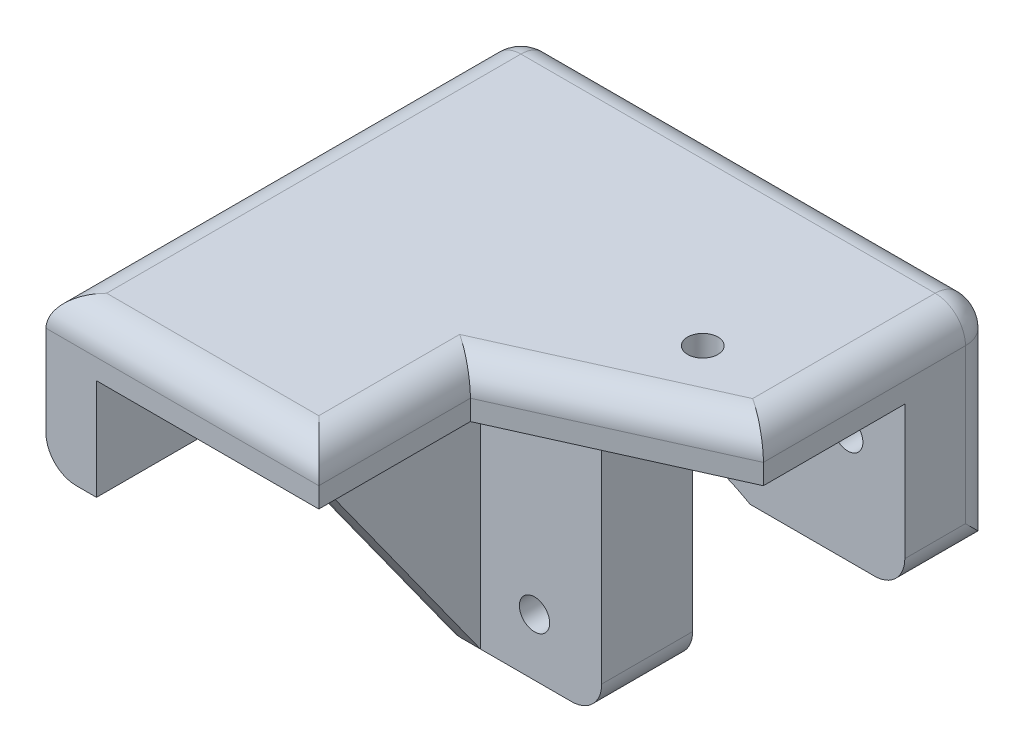
SolidWorks part; units mm, degrees
ref_plane "Front Plane" through (0, 0, 0) normal (0, 0, 1) x (1, 0, 0)
ref_plane "Top Plane" through (0, 0, 0) normal (0, 1, 0) x (1, 0, 0)
ref_plane "Right Plane" through (0, 0, 0) normal (1, 0, 0) x (0, 0, -1)
sketch "Sketch2" plane through (0, 0, 0) normal (0, 0, 1) x (1, 0, 0)
  line L0 (0, 0) -> (0, 47)
  line L1 (0, 47) -> (47, 47)
  line L2 (47, 47) -> (47, 25.75)
  line L3 (47, 25.75) -> (31.68, 25.75)
  line L4 (17, 0) -> (17, 27.58)
  line L5 (17, 0) -> (0, 0)
  arc A0 (17, 27.58) -> (31.68, 25.75) centre (22.2111, 9.5871) cw
  dimension "D1" = 47
  dimension "D2" = 47
  dimension "D3" = 21.25
  dimension "D4" = 17
  dimension "D5" = 27.58
  dimension "D6" = 15.32
extrude "Boss-Extrude1" add sketch "Sketch2" along normal blind 9
sketch "Sketch3" plane through (0, 0, 9) normal (0, 0, 1) x (1, 0, 0)
  line L0 (0, 0) -> (17, 0) construction
  line L1 (0, 47) -> (0, 0) construction
  line L3 (47, 47) -> (0, 47) construction
  circle A0 centre (10.35, 5.65) radius 1.5
  circle A1 centre (10.35, 36.65) radius 1.5
  circle A2 centre (41.35, 36.65) radius 1.5
  dimension "D1" = 3
  dimension "D5" = 3
  dimension "D6" = 3
  dimension "D2" = 5.65
  dimension "D3" = 10.35
  dimension "D4" = 31
  dimension "D7" = 10.35
  dimension "D8" = 31
extrude "Cut-Extrude1" cut sketch "Sketch3" against normal blind 10
sketch "Sketch4" plane through (0, 0, 9) normal (0, 0, 1) x (1, 0, 0)
  line L0 (47, 47) -> (0, 47) construction
  line L1 (0, 0) -> (5, 0)
  line L2 (0, 0) -> (0, 47)
  line L3 (0, 47) -> (5, 47)
  line L4 (5, 0) -> (5, 47)
  dimension "D1" = 5
extrude "Boss-Extrude2" add sketch "Sketch4" along normal blind 38
sketch "Sketch5" plane through (0, 0, 0) normal (-1, 0, 0) x (0, 0, 1)
  line L0 (47, 32) -> (32, 32)
  line L1 (47, 47) -> (47, 0) construction
  line L2 (32, 32) -> (9, 0)
  line L3 (47, 0) -> (0, 0) construction
  line L4 (9, 0) -> (47, 0)
  line L5 (47, 0) -> (47, 32)
  dimension "D1" = 9
  dimension "D2" = 15
  dimension "D3" = 15
extrude "Cut-Extrude2" cut sketch "Sketch5" against normal blind 38
sketch "Sketch6" plane through (0, 0, 9) normal (0, 0, 1) x (1, 0, 0)
  line L0 (47, 25.75) -> (47, 47) construction
  line L1 (5, 47) -> (47, 47)
  line L2 (5, 47) -> (5, 42)
  line L3 (5, 42) -> (47, 42)
  line L4 (47, 47) -> (47, 42)
  dimension "D1" = 5
extrude "Boss-Extrude3" add sketch "Sketch6" along normal blind 38
sketch "Sketch7" plane through (0, 0, 0) normal (0, 0, -1) x (-1, 0, 0)
  line L0 (0, 47) -> (0, 0) construction
  line L1 (0, 0) -> (-17, 0) construction
  circle A0 centre (-10, 20) radius 4
  dimension "D1" = 8
  dimension "D2" = 10
  dimension "D3" = 20
extrude "Cut-Extrude3" cut sketch "Sketch7" against normal blind 5
sketch "Sketch8" plane through (0, 42, 0) normal (0, -1, 0) x (-1, 0, 0)
  line L0 (-47, -9) -> (-47, -23)
  line L1 (-47, -47) -> (-47, -9) construction
  line L2 (-47, -23) -> (-27, -32)
  line L3 (-27, -32) -> (-27, -47)
  line L4 (-5, -47) -> (-47, -47) construction
  line L5 (-27, -47) -> (-47, -47)
  line L6 (-47, -47) -> (-47, -23)
  line M2 (-47, -9) -> (-47, -47)
  line M3 (-47, -47) -> (-5, -47)
  dimension "D1" = 14
  dimension "D2" = 20
  dimension "D3" = 15
extrude "Cut-Extrude4" cut sketch "Sketch8" against normal blind 10 contours L3 L2 M2 M3 region at (37.7692, 42, 37.0769)
fillet "Fillet1" radius 3 14 edges at (0, 32, 39.5) (0, 16, 20.5) (27, 47, 39.5) (37, 47, 27.5) (0, 23.5, 0) (47, 36.375, 0) (23.5, 47, 0) (0, 0, 4.5) (17, 0, 4.5) (17, 27.58, 4.5) (47, 25.75, 4.5) (47, 47, 11.5) (0, 47, 23.5) (13.5, 47, 47)
sketch "Sketch9" plane through (0, 42, 0) normal (0, -1, 0) x (-1, 0, 0)
  line L0 (-47, -23) -> (-47, -9) construction
  line L1 (-5, -9) -> (-47, -9) construction
  circle A0 centre (-37, -19) radius 1.5
  dimension "D3" = 3
  dimension "D1" = 10
  dimension "D2" = 10
extrude "Cut-Extrude5" cut sketch "Sketch9" against normal blind 10
sketch "Sketch10" plane through (0, 42, 0) normal (0, -1, 0) x (-1, 0, 0)
  circle A0 centre (-37, -19) radius 3
  dimension "D1" = 6
extrude "Cut-Extrude6" cut sketch "Sketch10" against normal blind 2
